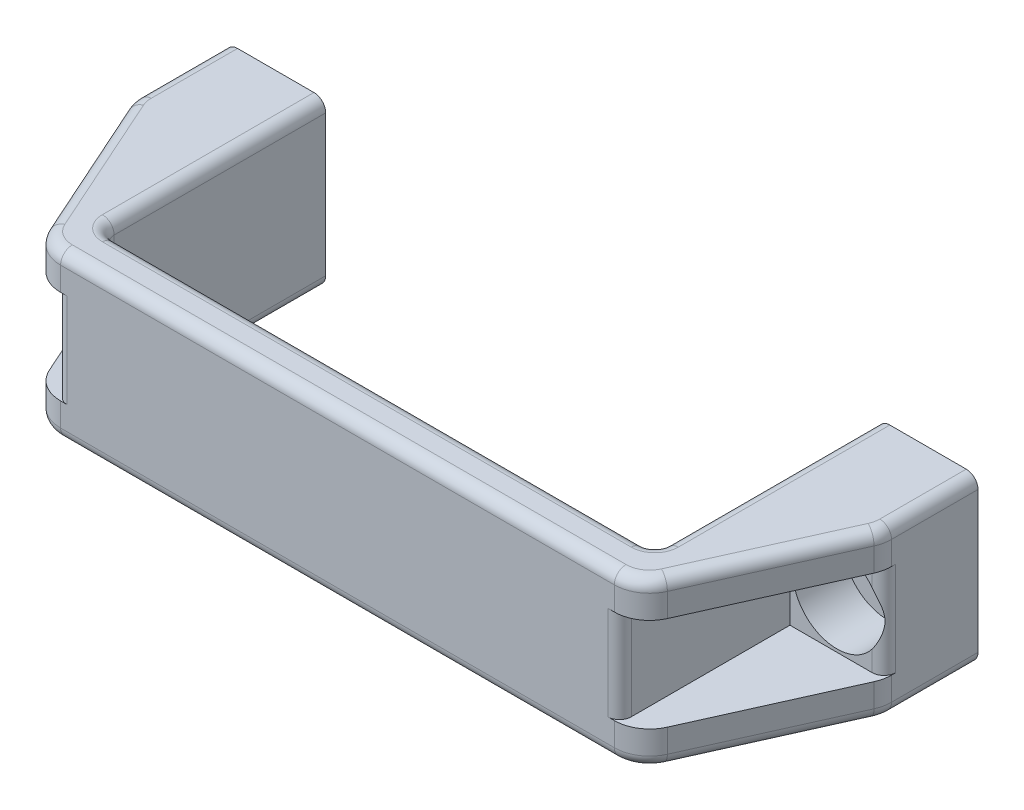
SolidWorks part; units mm, degrees
material "PVC Rigid"
ref_plane "Plan de face" through (0, 0, 0) normal (0, 0, 1) x (1, 0, 0)
ref_plane "Plan de dessus" through (0, 0, 0) normal (0, 1, 0) x (1, 0, 0)
ref_plane "Plan de droite" through (0, 0, 0) normal (1, 0, 0) x (0, 0, -1)
sketch "Sketch1" plane through (0, 0, 0) normal (0, 0, 1) x (1, 0, 0)
  line L1 (-64, -14) -> (64, -14)
  line L2 (-64, -14) -> (-64, 14)
  line L3 (-64, 14) -> (64, 14)
  line L4 (64, -14) -> (64, 14)
  line L5 (-64, -14) -> (64, 14) construction
  line L6 (-64, 14) -> (64, -14) construction
  point P0 (0, 0)
  dimension "D1" = 128
  dimension "D2" = 28
extrude "Boss-Extrude1" add sketch "Sketch1" along normal blind 45
sketch "Sketch2" plane through (0, -14, 0) normal (0, -1, 0) x (1, 0, 0)
  line L0 (-64, 0) -> (64, 0) construction
  line L2 (-47, 0) -> (-47, 38)
  line L3 (-47, 38) -> (47, 38)
  line L4 (47, 0) -> (47, 38)
  line L5 (-47, 0) -> (47, 38) construction
  line L6 (-47, 38) -> (47, 0) construction
  line L7 (-64, 45) -> (64, 45) construction
  line L8 (-51, 45) -> (51, 45)
  line L9 (51, 45) -> (64, 16)
  line L10 (64, 45) -> (64, 0) construction
  line L11 (-51, 45) -> (-64, 16)
  line L12 (-64, 45) -> (-64, 0) construction
  line L13 (-64, 16) -> (-64, 0)
  line L14 (-64, 0) -> (-47, 0)
  line L15 (47, 0) -> (64, 0)
  line L16 (64, 0) -> (64, 16)
  point P0 (0, 19)
  point P10 (0, 45)
  dimension "D1" = 94
  dimension "D2" = 38
  dimension "D3" = 16
  dimension "D4" = 16
  dimension "D5" = 102
  dimension "D6" = 13
extrude "Cut-Extrude2" cut sketch "Sketch2" against normal through all flip side to cut contours L2 L3 L4 L15 L16 L9 L8 L11 L13 L14
fillet "Fillet1" radius 6 4 edges at (-51, 0, 45) (-64, 0, 16) (51, 0, 45) (64, 0, 16)
fillet "Fillet2" radius 2 26 edges at (47, 14, 19) (-47, -14, 19) (0, 14, 38) (0, -14, 38) (64, 14, 7.3583) (63.8673, 14, 15.9716) (58.0322, 14, 29.3127) (50.3758, 14, 44.0362) (0, 14, 45) (-50.3758, 14, 44.0362) (-58.0322, 14, 29.3127) (-63.8673, 14, 15.9716) (-64, -14, 7.3583) (-63.8673, -14, 15.9716) (-58.0322, -14, 29.3127) (-50.3758, -14, 44.0362) (0, -14, 45) (50.3758, -14, 44.0362) (58.0322, -14, 29.3127) (63.8673, -14, 15.9716) (-47, 14, 19) (47, -14, 19) (-64, 14, 7.3583) (64, -14, 7.3583) (47, 0, 38) (-47, 0, 38)
sketch "Sketch3" plane through (0, 0, 45) normal (0, 0, 1) x (1, 0, 0)
  line L0 (-64, -12) -> (-64, 12) construction
  line L1 (-64, 8) -> (-48, 8)
  line L2 (-64, 8) -> (-64, -8)
  line L3 (-64, -8) -> (-48, -8)
  line L4 (-48, 8) -> (-48, -8)
  line L5 (64, 8) -> (48, 8)
  line L6 (64, 8) -> (64, -8)
  line L7 (64, -8) -> (48, -8)
  line L8 (48, 8) -> (48, -8)
  line L9 (64, 12) -> (64, -12) construction
  line L10 (-61.65, 14) -> (-50.7644, 14) construction
  dimension "D1" = 16
  dimension "D2" = 16
  dimension "D3" = 16
  dimension "D4" = 6
  dimension "D5" = 16
extrude "Cut-Extrude3" cut sketch "Sketch3" against normal blind 29
fillet "Fillet3" radius 2 4 edges at (63.8612, 0, 16) (48, 0, 44.9343) (-63.8612, 0, 16) (-48, 0, 44.9343)
hole_wizard "CBORE for M8 Hex Socket Head Cap Screw1" positions "Sketch4" profile "Sketch5" counterbore size "M8" standard "ISO"
sketch "Sketch4" plane through (0, 0, 16) normal (0, 0, 1) x (1, 0, 0)
  point P0 (-56, 0)
  point P2 (56, 0)
  dimension "D1" = 56
  dimension "D2" = 56
sketch "Sketch5" plane through (-56, 0, 16) normal (1, 0, 0) x (0, -1, 0)
  line L0 (0, 0) -> (0, 17.7039)
  line L1 (0, 17.7039) -> (4.5, 15)
  line L2 (4.5, 15) -> (4.5, 8.6)
  line L3 (4.5, 8.6) -> (7.5, 8.6)
  line L4 (7.5, 8.6) -> (7.5, 0)
  line L5 (7.5, 0) -> (0, 0)
  line L10 (0, 17.7039) -> (-4.5, 15) construction
  line L11 (0, -6.35) -> (0, 107.95) construction
  dimension "Hole Dia." = 9
  dimension "Hole Depth" = 15
  dimension "C'Bore Dia." = 15
  dimension "C'Bore Depth" = 8.6
  dimension "Drill Angle" = 118
